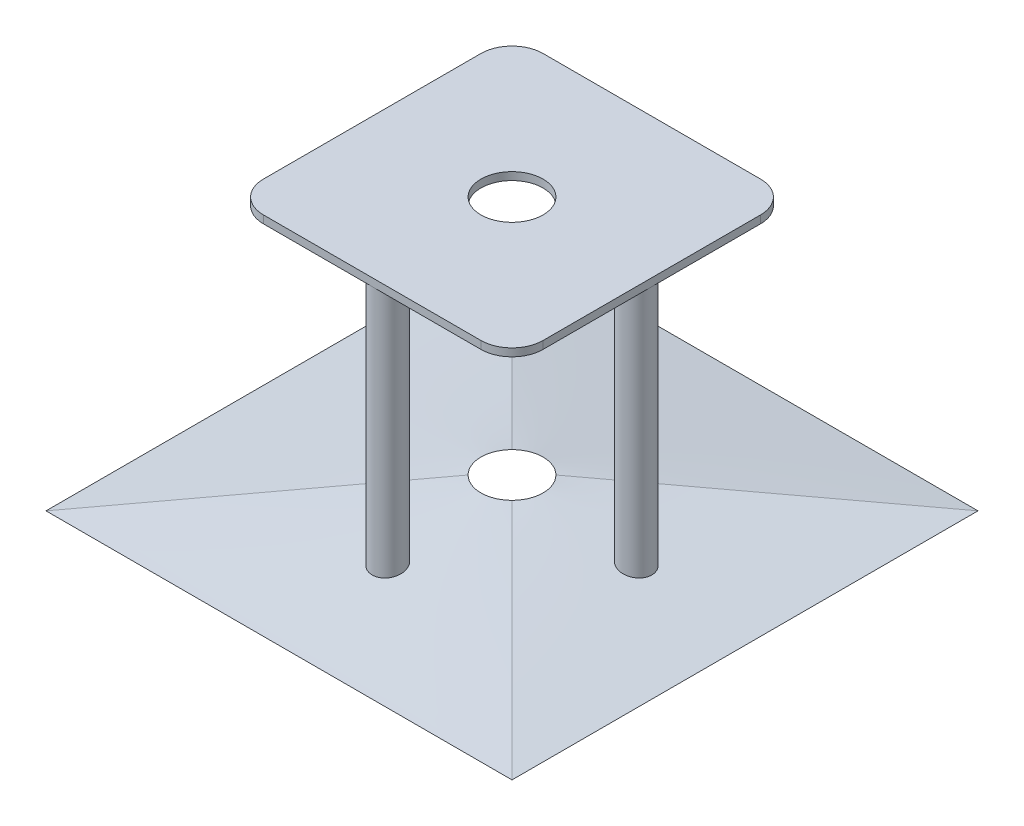
SolidWorks part; units mm, degrees
ref_plane "Front Plane" through (0, 0, 0) normal (0, 0, 1) x (1, 0, 0)
ref_plane "Top Plane" through (0, 0, 0) normal (0, 1, 0) x (1, 0, 0)
ref_plane "Right Plane" through (0, 0, 0) normal (1, 0, 0) x (0, 0, -1)
sketch "Sketch1" plane through (0, 0, 0) normal (0, 1, 0) x (1, 0, 0)
  line L1 (75, -75) -> (-75, -75)
  line L2 (75, -75) -> (75, 75)
  line L3 (75, 75) -> (-75, 75)
  line L4 (-75, -75) -> (-75, 75)
  line L5 (75, -75) -> (-75, 75) construction
  line L6 (75, 75) -> (-75, -75) construction
  point P0 (0, 0)
  dimension "D1" = 150
  dimension "D2" = 150
ref_plane "Plane1" through (0, 10, 0) normal (0, 1, 0) x (1, 0, 0)
sketch "Sketch2" plane through (0, 10, 0) normal (0, 1, 0) x (1, 0, 0)
  circle A0 centre (0, 0) radius 10
  dimension "D1" = 20
loft "Loft1" add profiles "Sketch1", "Sketch2" connector at (-75, 0, 75) connector at (0, 10, 10)
sketch "Sketch3" plane through (0, 10, 0) normal (0, 1, 0) x (1, 0, 0)
  circle A0 centre (0, 0) radius 10
extrude "Cut-Extrude1" cut sketch "Sketch3" against normal through all and the other way through all
sketch "Sketch4" plane through (0, 0, 0) normal (0, 1, 0) x (1, 0, 0)
  line L0 (75, 75) -> (7.0711, 7.0711) construction
  line L1 (-72.5, -72.5) -> (72.5, -72.5)
  line L2 (-72.5, -72.5) -> (-72.5, 72.5)
  line L3 (-72.5, 72.5) -> (72.5, 72.5)
  line L4 (72.5, -72.5) -> (72.5, 72.5)
  line L5 (-72.5, -72.5) -> (72.5, 72.5) construction
  line L6 (-72.5, 72.5) -> (72.5, -72.5) construction
  point P0 (0, 0)
  dimension "D1" = 145
  dimension "D2" = 145
loft "Cut-Loft2" cut profiles "Sketch4", "Sketch2<5>" connector at (-72.5, 0, -72.5) connector at (-9.9196, 10, 1.2658)
sketch "Sketch2<5>" plane through (0, 10, 0) normal (0, 1, 0) x (1, 0, 0) same geometry as "Sketch2"
sketch "Sketch5" plane through (0, 0, 0) normal (1, 0, 0) x (0, 0, -1)
  line L0 (-42.5, 5) -> (-42.5, 85) construction
  line L1 (-10, 10) -> (-75, 0) construction
  line L2 (41.0355, 5) -> (41.0355, 85) construction
  line L3 (75, 0) -> (7.0711, 10) construction
  dimension "D1" = 80
sketch "Sketch6" plane through (0, 0, 0) normal (0, 0, 1) x (1, 0, 0)
  line L0 (-41.0355, 5) -> (-41.0355, 85) construction
  line L1 (-7.0711, 10) -> (-75, 0) construction
  line L2 (41.0355, 5) -> (41.0355, 85) construction
  line L3 (75, 0) -> (7.0711, 10) construction
  dimension "D1" = 80
ref_plane "Plane3" through (0, 85, 0) normal (0, -1, 0) x (-1, 0, 0)
sketch "Sketch11" plane through (0, 85, 0) normal (0, -1, 0) x (-1, 0, 0)
  line L0 (-40.4624, 0) -> (40.2437, 0) construction
  line L1 (0, 42.2121) -> (0, -42.2121) construction
  line L2 (-72.5, 72.5) -> (-7.0711, 7.0711) construction
  line L3 (45, -45) -> (-45, -45)
  line L4 (45, -45) -> (45, 45)
  line L5 (45, 45) -> (-45, 45)
  line L6 (-45, -45) -> (-45, 45)
  line L7 (45, -45) -> (-45, 45) construction
  line L8 (45, 45) -> (-45, -45) construction
  point P5 (0, 0)
  dimension "D1" = 90
  dimension "D2" = 90
extrude "Boss-Extrude1" add sketch "Sketch11" against normal blind 2.5 separate body
sketch "Sketch16" plane through (0, 87.5, 0) normal (0, 1, 0) x (1, 0, 0)
  line L0 (-45, 45) -> (-45, -45) construction
  line L1 (-7.0711, -7.0711) -> (-75, -75) construction
  line L2 (-45, -45) -> (45, -45) construction
  line L3 (75, -75) -> (7.0711, -7.0711) construction
  line L4 (45, -45) -> (-45, -45) construction
  line L5 (45, -45) -> (45, 45) construction
  line L6 (75, 75) -> (7.0711, 7.0711) construction
  line L7 (-45, 45) -> (45, 45) construction
  line L8 (45, 45) -> (-45, 45) construction
  line L9 (0, -45) -> (0, 45) construction
  line L10 (-45, 0) -> (45, 0) construction
  line L11 (0, 45) -> (0, 40) construction
  line L12 (45, 0) -> (40, 0) construction
  line L13 (-45, 0) -> (-40, 0) construction
  line L14 (0, -45) -> (0, -40) construction
  circle A0 centre (0, 40) radius 5
  circle A1 centre (-40, 0) radius 5
  circle A2 centre (0, -40) radius 5
  circle A3 centre (40, 0) radius 5
  dimension "D1" = 5
  dimension "D2" = 5
extrude "Boss-Extrude2" add sketch "Sketch16" against normal up to body from surface starting at face at (0, 85, 0)
extrude "Cut-Extrude2" cut sketch "Sketch3<2>" along normal through all
sketch "Sketch3<2>" plane through (0, 10, 0) normal (0, 1, 0) x (1, 0, 0) same geometry as "Sketch3"
fillet "Fillet1" radius 10 4 edges at (-45, 86.25, -45) (-45, 86.25, 45) (45, 86.25, 45) (45, 86.25, -45)
